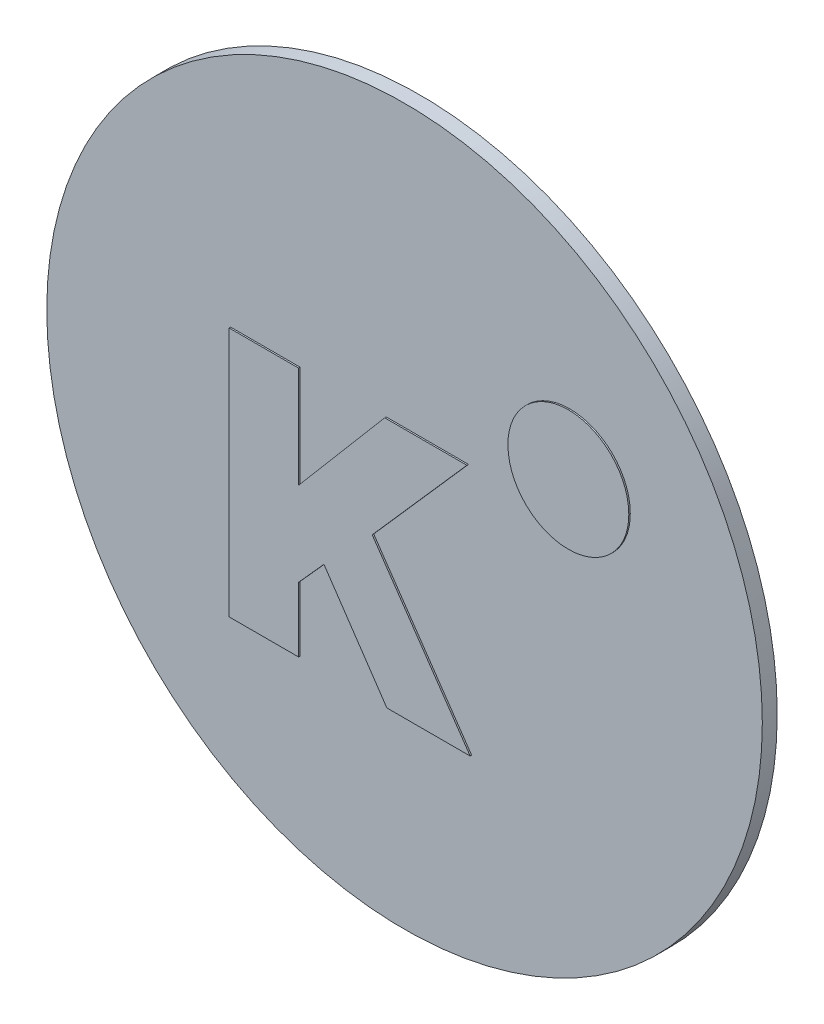
SolidWorks part; units mm, degrees
material "Сплав 2024"
ref_plane "Спереди" through (0, 0, 0) normal (0, 0, 1) x (1, 0, 0)
ref_plane "Сверху" through (0, 0, 0) normal (0, 1, 0) x (1, 0, 0)
ref_plane "Справа" through (0, 0, 0) normal (1, 0, 0) x (0, 0, -1)
sketch "Эскиз1" plane through (0, 0, 0) normal (0, 0, 1) x (1, 0, 0)
  circle A0 centre (0, 0) radius 24
  dimension "D1" = 48
extrude "Бобышка-Вытянуть1" add sketch "Эскиз1" along normal blind 1
sketch "Эскиз2" plane through (0, 0, 1) normal (0, 0, 1) x (1, 0, 0)
  line B0 (7.0372, 7.7071) -> (7.0372, 7.7553)
  line B1 (15.141, 7.7553) -> (15.141, 7.7071)
  line B2 (-11.6596, 5.1573) -> (-7.0084, 5.1573)
  line B3 (-7.0084, 5.1573) -> (-7.0084, -1.6519)
  line B4 (-7.0084, -1.6519) -> (-1.2299, 5.1573)
  line B5 (-1.2299, 5.1573) -> (4.2847, 5.1573)
  line B6 (4.2847, 5.1573) -> (-2.069, -2.0595)
  line B7 (-2.069, -2.0595) -> (4.5004, -11.6261)
  line B8 (4.5004, -11.6261) -> (-1.0862, -11.6261)
  line B9 (-1.0862, -11.6261) -> (-5.306, -5.3922)
  line B10 (-5.306, -5.3922) -> (-7.0084, -7.2863)
  line B11 (-7.0084, -7.2863) -> (-7.0084, -11.6261)
  line B12 (-7.0084, -11.6261) -> (-11.6596, -11.6261)
  line B13 (-11.6596, -11.6261) -> (-11.6596, 5.1573)
  spline B14 degree 3 poles (7.0372, 7.7553) (7.0372, 9.985) (8.8592, 11.7831) (11.0889, 11.7831) knots 1 1 1 1 2 2 2 2
  spline B15 degree 3 poles (11.0889, 11.7831) (13.3188, 11.7831) (15.141, 9.985) (15.141, 7.7553) knots 2 2 2 2 3 3 3 3
  spline B16 degree 3 poles (15.141, 7.7071) (15.141, 5.4774) (13.3188, 3.6793) (11.0889, 3.6793) knots 4 4 4 4 5 5 5 5
  spline B17 degree 3 poles (11.0889, 3.6793) (8.8592, 3.6793) (7.0372, 5.4774) (7.0372, 7.7071) knots 5 5 5 5 6 6 6 6
sketch_block_instance "Блок2-1"
sketch_block "Блок2"
extrude "Бобышка-Вытянуть2" add sketch "Эскиз2" along normal blind 0.1 separate body
